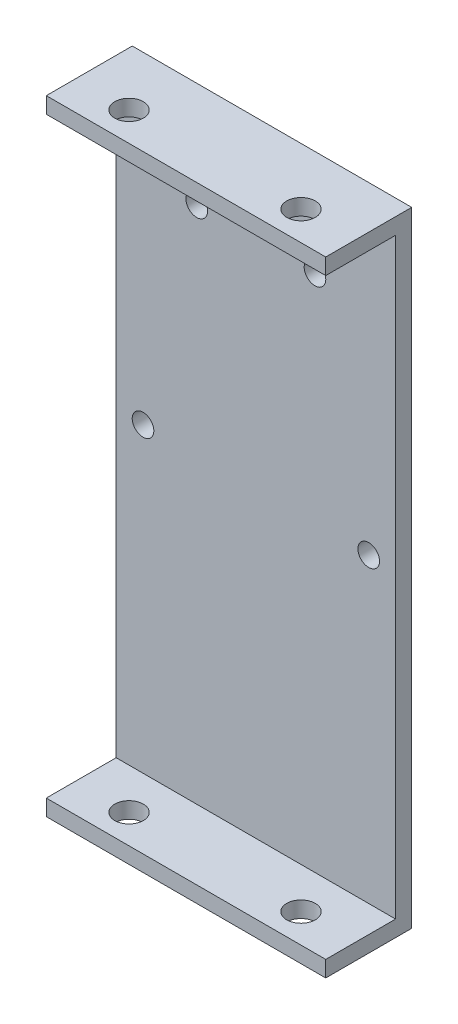
SolidWorks part; units mm, degrees
ref_plane "Front Plane" through (0, 0, 0) normal (0, 0, 1) x (1, 0, 0)
ref_plane "Top Plane" through (0, 0, 0) normal (0, 1, 0) x (1, 0, 0)
ref_plane "Right Plane" through (0, 0, 0) normal (1, 0, 0) x (0, 0, -1)
sketch "Sketch1" plane through (0, 0, 0) normal (0, 0, 1) x (1, 0, 0)
  line L0 (66.04, 81.2371) -> (66.04, 68.7911) construction
  line L1 (0, 0) -> (66.04, 0)
  line L2 (0, 0) -> (0, 147.574)
  line L3 (0, 147.574) -> (66.04, 147.574)
  line L4 (66.04, 0) -> (66.04, 147.574)
  dimension "D2" = 147.574
extrude "Boss-Extrude1" add sketch "Sketch1" along normal blind 3.81
sketch "Sketch3" plane through (0, 0, 3.81) normal (0, 0, 1) x (1, 0, 0)
  line L0 (66.04, 0) -> (66.04, 147.574) construction
  line L1 (0, 147.574) -> (66.04, 147.574)
  line L2 (0, 147.574) -> (0, 143.764)
  line L3 (0, 143.764) -> (66.04, 143.764)
  line L4 (66.04, 147.574) -> (66.04, 143.764)
  line L6 (0, 0) -> (66.04, 0)
  line L7 (0, 0) -> (0, 3.81)
  line L8 (0, 3.81) -> (66.04, 3.81)
  line L9 (66.04, 0) -> (66.04, 3.81)
  dimension "D1" = 3.81
  dimension "D2" = 3.81
extrude "Boss-Extrude2" add sketch "Sketch3" along normal blind 16.51
sketch "Sketch4" plane through (0, 0, 0) normal (0, -1, 0) x (1, 0, 0)
  line L0 (0, 20.32) -> (66.04, 20.32) construction
  line L3 (0, 20.32) -> (0, 0) construction
  circle A0 centre (12.7, 13.462) radius 3.3782
  circle A5 centre (53.34, 13.462) radius 3.3782
  dimension "D2" = 6.7564
  dimension "D3" = 6.7564
  dimension "D4" = 6.858
  dimension "D6" = 6.858
  dimension "D1" = 40.64
  dimension "D5" = 12.7
extrude "Cut-Extrude1" cut sketch "Sketch4" against normal through all
sketch "Sketch5" plane through (0, 0, 3.81) normal (0, 0, 1) x (1, 0, 0)
  circle A0 centre (46.99, 126.4491) radius 2.5527 construction
  circle A1 centre (19.05, 126.4491) radius 2.5527 construction
  circle A2 centre (6.35, 75.1411) radius 2.5527 construction
  circle A3 centre (59.69, 75.1411) radius 2.5527 construction
  circle A4 centre (46.99, 126.4491) radius 2.5527
  circle A5 centre (19.05, 126.4491) radius 2.5527
  circle A6 centre (6.35, 75.1411) radius 2.5527
  circle A7 centre (59.69, 75.1411) radius 2.5527
extrude "Cut-Extrude2" cut sketch "Sketch5" against normal up to surface (3.81 mm away) up to face at (33.02, 73.787, 0)
